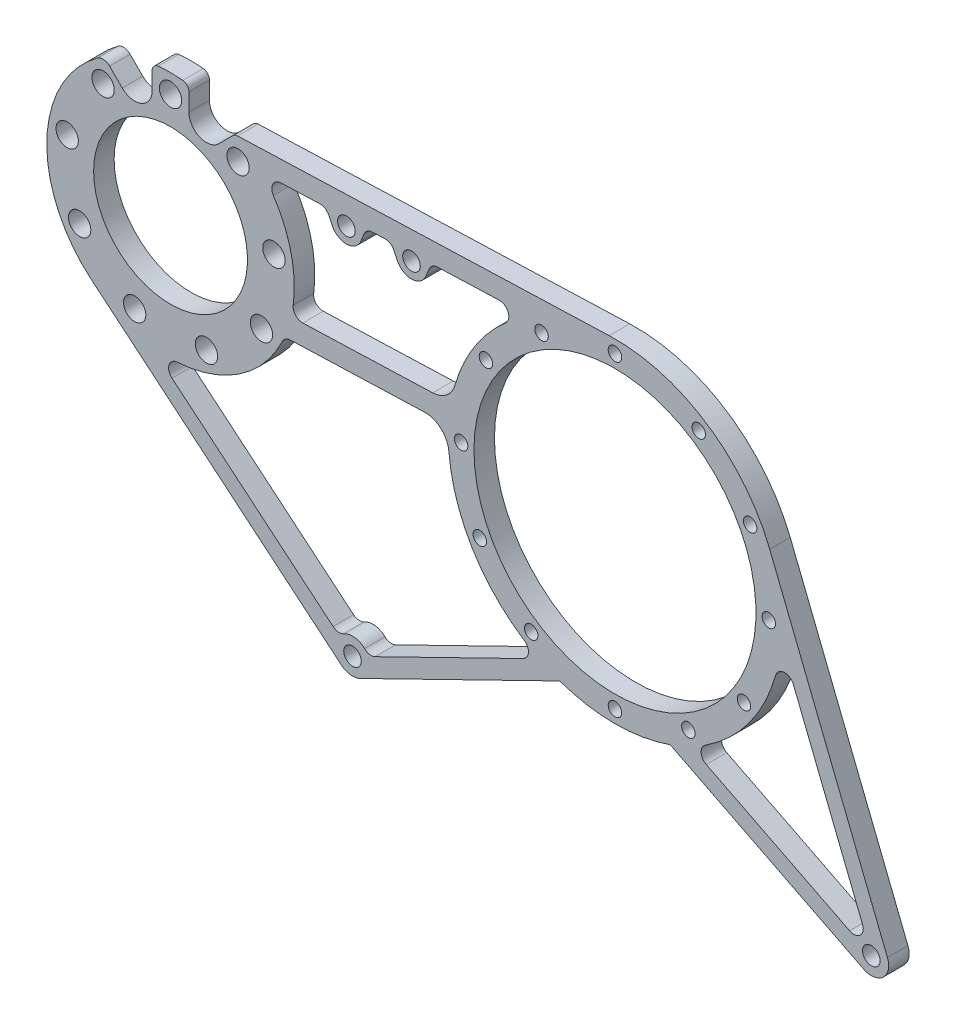
SolidWorks part; units mm, degrees
material "6061-T6 (SS)"
ref_plane "Front Plane" through (0, 0, 0) normal (0, 0, 1) x (1, 0, 0)
ref_plane "Top Plane" through (0, 0, 0) normal (0, 1, 0) x (1, 0, 0)
ref_plane "Right Plane" through (0, 0, 0) normal (1, 0, 0) x (0, 0, -1)
sketch "Sketch2" plane through (0, 0, 0) normal (0, 0, 1) x (1, 0, 0)
  line L0 (-114.3, 107.95) -> (-114.3, 95.25) construction
  line L1 (-308.8661, 91.7104) -> (-215.9264, 14.1075)
  line L3 (-13.0706, 21.4387) -> (-56.8054, 130.918)
  line L4 (-208.9705, 13.2659) -> (-134.815, 49.5352)
  line L5 (-21.9498, 13.301) -> (-93.785, 49.5352)
  line L7 (-254.4917, 165.0591) -> (-116.4363, 169.8256)
  line L10 (-286.2388, 170.2207) -> (-286.2388, 163.648)
  line L11 (-299.2388, 163.648) -> (-299.2388, 164.225)
  line L12 (-256.2001, 164.3167) -> (-261.465, 159.0518)
  line L13 (-272.5612, 163.648) -> (-272.5612, 170.2207)
  line L14 (-286.2388, 170.2207) -> (-286.2388, 163.648)
  line L16 (-256.2001, 164.3167) -> (-261.465, 159.0518)
  line L17 (-272.5612, 163.648) -> (-272.5612, 170.2207)
  line L84 (-302.5999, 164.3167) -> (-297.335, 159.0518) construction
  line L85 (-302.028, 163.7448) -> (-297.335, 159.0518)
  circle A0 centre (-279.4, 127) radius 28.575
  circle A1 centre (-114.3, 95.25) radius 36 construction
  circle A2 centre (0, 0) radius 12.7 construction
  circle A3 centre (-228.6, 0) radius 12.7 construction
  arc A5 (-134.815, 49.5352) -> (-93.785, 49.5352) centre (-114.3, 107.95) ccw
  circle A6 centre (-19.05, 19.05) radius 3.2639
  circle A7 centre (-211.7995, 19.05) radius 3.2639
  arc A8 (-215.9264, 14.1075) -> (-208.9705, 13.2659) centre (-211.7995, 19.05) ccw
  arc A9 (-21.9498, 13.301) -> (-13.0706, 21.4387) centre (-19.05, 19.05) ccw
  circle A10 centre (-114.3, 107.95) radius 52.3875
  arc A11 (-56.8054, 130.918) -> (-116.4363, 169.8256) centre (-114.3, 107.95) ccw
  arc A12 (-134.815, 49.5352) -> (-116.4363, 169.8256) centre (-114.3, 107.95) ccw construction
  arc A13 (-308.8661, 91.7104) -> (-306.5609, 164.0931) centre (-279.4, 127) cw
  arc A20 (-299.2388, 163.648) -> (-286.2388, 163.648) centre (-292.7388, 163.648) ccw
  arc A21 (-299.2388, 164.225) -> (-303.0875, 166.4019) centre (-301.7788, 164.225) ccw
  arc A22 (-303.0875, 166.4019) -> (-252.9423, 164.5979) centre (-279.4, 127) ccw
  arc A23 (-252.9423, 164.5979) -> (-256.2001, 164.3167) centre (-254.4041, 162.5207) ccw
  arc A24 (-272.5612, 163.648) -> (-261.465, 159.0518) centre (-266.0612, 163.648) ccw
  arc A25 (-272.5612, 170.2207) -> (-274.8498, 172.7483) centre (-275.1012, 170.2207) ccw
  arc A26 (-274.8498, 172.7483) -> (-283.9502, 172.7483) centre (-279.4, 127) ccw
  arc A27 (-283.9502, 172.7483) -> (-286.2388, 170.2207) centre (-283.6988, 170.2207) ccw
  arc A28 (-297.335, 159.0518) -> (-286.2388, 163.648) centre (-292.7388, 163.648) ccw
  arc A31 (-254.4917, 165.0591) -> (-256.2001, 164.3167) centre (-254.4041, 162.5207) ccw
  arc A32 (-272.5612, 163.648) -> (-261.465, 159.0518) centre (-266.0612, 163.648) ccw
  arc A33 (-272.5612, 170.2207) -> (-274.8498, 172.7483) centre (-275.1012, 170.2207) ccw
  arc A34 (-274.8498, 172.7483) -> (-283.9502, 172.7483) centre (-279.4, 127) ccw
  arc A35 (-283.9502, 172.7483) -> (-286.2388, 170.2207) centre (-283.6988, 170.2207) ccw
  arc A166 (-306.5609, 164.0931) -> (-302.028, 163.7448) centre (-304.4975, 161.2752) cw
  dimension "D1" = 25.4
  dimension "D2" = 25.4
  dimension "D8" = 57.15
  dimension "D9" = 72
  dimension "D10" = 3.4925
  dimension "D12" = 123.825
  dimension "D13" = 6.5278
  dimension "D16" = 6.5278
  dimension "D18" = 3.175
  dimension "D20" = 104.775
  dimension "D3" = 228.6
  dimension "D4" = 114.3
  dimension "D5" = 95.25
  dimension "D6" = 279.4
  dimension "D7" = 127
  dimension "D11" = 12.7
  dimension "D14" = 19.05
  dimension "D15" = 19.05
  dimension "D17" = 25.4
  dimension "D19" = 82.55
  dimension "D21" = 0
extrude "Boss-Extrude1" add sketch "Sketch2" along normal blind 7.62
sketch "Sketch3" plane through (0, 0, 7.62) normal (0, 0, 1) x (1, 0, 0)
  line L0 (-279.4, 127) -> (-279.4, 166) construction
  line L1 (-114.3, 107.95) -> (-114.3, 165.1) construction
  line L2 (-114.3, 107.95) -> (-83.1739, 155.88) construction
  line L3 (-114.3, 107.95) -> (-64.0756, 135.2196) construction
  circle A0 centre (-279.4, 127) radius 39 construction
  circle A1 centre (-279.4, 166) radius 4.15
  circle A2 centre (-254.3313, 156.8757) radius 4.15
  circle A3 centre (-240.9925, 133.7723) radius 4.15
  circle A4 centre (-245.625, 107.5) radius 4.15
  circle A5 centre (-266.0612, 90.352) radius 4.15
  circle A6 centre (-292.7388, 90.352) radius 4.15
  circle A7 centre (-313.175, 107.5) radius 4.15
  circle A8 centre (-317.8075, 133.7723) radius 4.15
  circle A9 centre (-304.4687, 156.8757) radius 4.15
  circle A10 centre (-114.3, 107.95) radius 57.15 construction
  circle A11 centre (-114.3, 165.1) radius 2.5
  circle A21 centre (-57.15, 107.95) radius 2.5
  circle A22 centre (-114.3, 50.8) radius 2.5
  circle A23 centre (-171.45, 107.95) radius 2.5
  circle A24 centre (-83.1739, 155.88) radius 2.5
  circle A25 centre (-64.0756, 135.2196) radius 2.5
  circle A26 centre (-66.37, 76.8239) radius 2.5
  circle A27 centre (-87.0304, 57.7256) radius 2.5
  circle A28 centre (-145.4261, 60.02) radius 2.5
  circle A29 centre (-164.5244, 80.6804) radius 2.5
  circle A30 centre (-162.23, 139.0761) radius 2.5
  circle A31 centre (-141.5696, 158.1744) radius 2.5
  point P24 (-279.4, 127)
  point P36 (-114.3, 107.95)
  point P48 (-114.3, 107.95)
  point P54 (-114.3, 107.95)
  dimension "D1" = 78
  dimension "D2" = 8.3
  dimension "D4" = 114.3
  dimension "D5" = 5
  dimension "D7" = 33
  dimension "D8" = 61.5
  dimension "D3" = 9
  dimension "D6" = 4
  dimension "D9" = 4
extrude "Cut-Extrude1" cut sketch "Sketch3" against normal through all both and the other way through all
sketch "Sketch4" plane through (0, 0, 7.62) normal (0, 0, 1) x (1, 0, 0)
  line L0 (-278.8626, 74.9306) -> (-219.0181, 24.9616)
  line L1 (-48.0193, 91.8071) -> (-22.3039, 27.4349)
  line L2 (-308.8661, 91.7104) -> (-215.9264, 14.1075) construction
  line L3 (-148.3931, 49.9629) -> (-203.3792, 23.0694)
  line L4 (-208.9705, 13.2659) -> (-134.815, 49.5352) construction
  line L5 (-238.4024, 157.9901) -> (-157.3456, 160.7887)
  line L7 (-80.3879, 49.8896) -> (-27.12, 23.021)
  line L8 (-93.785, 49.5352) -> (-21.9498, 13.301) construction
  line L9 (-13.0706, 21.4387) -> (-56.8054, 130.918) construction
  line L10 (-230.2469, 116.9721) -> (-182.0371, 118.6366)
  line L11 (-234.876, 109.1877) -> (-185.1604, 110.9042)
  line L13 (-116.4363, 169.8256) -> (-254.4917, 165.0591) construction
  arc A0 (-233.8293, 120.9241) -> (-237.9076, 107.2013) centre (-279.4, 127) ccw construction
  arc A1 (-175.9949, 102.7641) -> (-173.8002, 125.0639) centre (-114.3, 107.95) ccw construction
  circle A2 centre (-19.05, 19.05) radius 6.4389 construction
  circle A3 centre (-211.7995, 19.05) radius 6.4389 construction
  arc A4 (-306.5609, 164.0931) -> (-308.8661, 91.7104) centre (-279.4, 127) ccw construction
  arc A5 (-241.1849, 152.5581) -> (-233.8293, 120.9241) centre (-279.4, 127) cw
  arc A6 (-154.933, 154.6631) -> (-173.8002, 125.0639) centre (-114.3, 107.95) ccw
  arc A7 (-54.6287, 91.4427) -> (-80.7099, 55.9417) centre (-114.3, 107.95) cw
  arc A8 (-157.3456, 160.7887) -> (-154.933, 154.6631) centre (-157.2251, 157.2982) cw
  arc A9 (-238.4024, 157.9901) -> (-241.1849, 152.5581) centre (-238.2818, 154.4997) ccw
  arc A10 (-278.8626, 74.9306) -> (-276.8202, 81.0984) centre (-276.6242, 77.6114) cw
  arc A11 (-148.0251, 56.0292) -> (-148.3931, 49.9629) centre (-149.9276, 53.1003) cw
  arc A12 (-80.3879, 49.8896) -> (-80.7099, 55.9417) centre (-78.8151, 53.0079) cw
  arc A13 (-48.0193, 91.8071) -> (-54.6287, 91.4427) centre (-51.2626, 90.5115) ccw
  arc A14 (-27.12, 23.021) -> (-22.3039, 27.4349) centre (-25.5472, 26.1393) ccw
  arc A15 (-215.0283, 24.6208) -> (-207.3352, 23.69) centre (-211.7995, 19.05) cw
  arc A16 (-203.3792, 23.0694) -> (-207.3352, 23.69) centre (-204.9137, 26.2067) cw
  arc A17 (-219.0181, 24.9616) -> (-215.0283, 24.6208) centre (-216.7797, 27.6425) ccw
  arc A18 (-237.9076, 107.2013) -> (-276.8202, 81.0984) centre (-279.4, 127) cw
  arc A19 (-175.9949, 102.7641) -> (-148.0251, 56.0292) centre (-114.3, 107.95) ccw
  arc A22 (-230.2469, 116.9721) -> (-233.8293, 120.9241) centre (-230.3674, 120.4625) cw
  arc A23 (-234.876, 109.1877) -> (-237.9076, 107.2013) centre (-234.7555, 105.6973) ccw
  arc A24 (-182.0371, 118.6366) -> (-173.8002, 125.0639) centre (-182.3438, 127.5213) ccw
  arc A25 (-185.1604, 110.9042) -> (-175.9949, 102.7641) centre (-184.8537, 102.0195) cw
  point P40 (-245.2273, 157.7545)
  point P43 (-286.9003, 81.6419)
  point P46 (-142.5125, 52.8391)
  point P50 (-52.5701, 103.1988)
  point P56 (-216.7985, 23.1083)
  dimension "D1" = 61.9125
  dimension "D2" = 12.8778
  dimension "D3" = 12.8778
  dimension "D9" = 3.4925
  dimension "D10" = 61.9125
  dimension "D11" = 3.4925
  dimension "D14" = 8.89
  dimension "D15" = 8.89
  dimension "D4" = 6.35
  dimension "D5" = 6.35
  dimension "D6" = 7.62
  dimension "D7" = 6.35
  dimension "D8" = 6.35
  dimension "D12" = 41.275
  dimension "D13" = 7.62
extrude "Cut-Extrude2" cut sketch "Sketch4" against normal through all both and the other way through all
sketch "Sketch6" plane through (0, 0, 7.62) normal (0, 0, 1) x (1, 0, 0)
  line L0 (-256.2001, 164.3171) -> (-261.465, 159.0522)
  line L1 (-272.5612, 163.6484) -> (-272.5612, 170.2212)
  line L2 (-286.2388, 170.2212) -> (-286.2388, 163.6484)
  line L3 (-299.2388, 163.6484) -> (-299.2392, 164.2676)
  arc A0 (-303.0807, 166.406) -> (-252.9493, 164.6028) centre (-279.4, 127) ccw
  arc A1 (-252.9493, 164.6028) -> (-256.2001, 164.3171) centre (-254.4043, 162.5208) ccw
  arc A2 (-272.5612, 163.6484) -> (-261.465, 159.0522) centre (-266.0612, 163.6484) ccw
  arc A3 (-272.5612, 170.2212) -> (-274.8498, 172.7487) centre (-275.1012, 170.2212) ccw
  arc A4 (-274.8498, 172.7487) -> (-283.9502, 172.7487) centre (-279.4, 127.0004) ccw
  arc A5 (-283.9502, 172.7487) -> (-286.2388, 170.2212) centre (-283.6988, 170.2212) ccw
  arc A6 (-299.2388, 163.6484) -> (-286.2388, 163.6484) centre (-292.7388, 163.6484) ccw
  arc A7 (-299.2392, 164.2676) -> (-303.0807, 166.406) centre (-301.7788, 164.225) ccw
  dimension "D1" = 45.974
  dimension "D2" = 2.54
  dimension "D4" = 6.5
  dimension "D5" = 6.5
  dimension "D6" = 2.54
  dimension "D7" = 2.54
  dimension "D8" = 45.974
  dimension "D9" = 2.54
  dimension "D3" = 7.4457
  dimension "D10" = 6.5727
ref_plane "Plane3" through (0, 0, 3.81) normal (0, 0, 1) x (1, 0, 0)
ref_axis "Axis1" through (-279.4, 127, 7.62) along (0, 0, -1)
ref_plane "Plane1" through (-279.4, 0, 0) normal (1, 0, 0) x (0, 0, -1)
ref_axis "Axis2" through (-114.3, 107.95, 7.62) along (0, 0, -1)
ref_plane "Plane2" through (-114.3, 0, 0) normal (1, 0, 0) x (0, 0, -1)
split line "Split Line1" [suppressed]
split line "Split Line2" [suppressed]
sketch "Sketch7" [suppressed] plane through (0, 0, 3.81) normal (0, 0, 1) x (1, 0, 0)
  arc A0 (-279.4, 155.575) -> (-279.4, 98.425) centre (-279.4, 127) ccw construction
  arc A1 (-279.4, 98.425) -> (-279.4, 155.575) centre (-279.4, 127) ccw construction
  arc A2 (-279.4, 155.575) -> (-279.4, 98.425) centre (-279.4, 127) ccw
  arc A3 (-279.4, 98.425) -> (-279.4, 155.575) centre (-279.4, 127) ccw
  arc A4 (-114.3, 55.5625) -> (-114.3, 160.3375) centre (-114.3, 107.95) ccw construction
  arc A5 (-114.3, 160.3375) -> (-114.3, 55.5625) centre (-114.3, 107.95) ccw construction
  arc A6 (-114.3, 55.5625) -> (-114.3, 160.3375) centre (-114.3, 107.95) ccw
  arc A7 (-114.3, 160.3375) -> (-114.3, 55.5625) centre (-114.3, 107.95) ccw
  point P4 (-279.4, 127)
  point P8 (-114.3, 107.95)
sketch "Sketch11" plane through (0, 0, 0) normal (0, 0, -1) x (-1, 0, 0)
  line L0 (157.3456, 160.7887) -> (238.4024, 157.9901) construction
  line L1 (182.3987, 159.9237) -> (187.9461, 159.7321)
  line L2 (184.5049, 154.9364) -> (183.3433, 157.8152)
  line L3 (189.8872, 157.1081) -> (189.9754, 159.6621) construction
  line L4 (195.1068, 154.5703) -> (196.4642, 157.3621)
  line L5 (201.9791, 156.6907) -> (202.2057, 163.2538) construction
  line L6 (189.8872, 157.1081) -> (214.071, 156.2732) construction
  line L7 (208.6887, 154.1014) -> (207.5271, 156.9802)
  line L8 (214.071, 156.2732) -> (214.1591, 158.8271)
  line L9 (219.2906, 153.7354) -> (220.648, 156.5272)
  line L10 (221.7357, 158.5656) -> (206.5825, 159.0887)
  line L11 (223.9095, 158.4905) -> (221.7357, 158.5656)
  line L12 (197.552, 159.4005) -> (199.7256, 159.3254)
  line L13 (206.5825, 159.0887) -> (204.4088, 159.1638)
  line L14 (182.3987, 159.9237) -> (180.2251, 159.9987)
  line L15 (192.0046, 159.592) -> (197.552, 159.4005)
  arc A0 (187.9461, 159.7321) -> (192.0046, 159.592) centre (189.8872, 157.1081) ccw
  circle A1 centre (214.071, 156.2732) radius 3.3 construction
  arc A2 (184.5049, 154.9364) -> (195.1068, 154.5703) centre (189.8872, 157.1081) ccw
  circle A4 centre (189.8872, 157.1081) radius 5.8039 construction
  circle A5 centre (189.8872, 157.1081) radius 3.2639 construction
  arc A6 (219.2906, 153.7354) -> (208.6887, 154.1014) centre (214.071, 156.2732) cw
  arc A7 (216.1884, 158.7571) -> (212.1299, 158.8972) centre (214.071, 156.2732) cw
  arc A8 (183.3433, 157.8152) -> (180.2251, 159.9987) centre (180.1045, 156.5083) ccw
  arc A9 (223.9095, 158.4905) -> (220.648, 156.5272) centre (223.7889, 155.0001) ccw
  arc A10 (207.5271, 156.9802) -> (204.4088, 159.1638) centre (204.2883, 155.6733) ccw
  arc A11 (199.7256, 159.3254) -> (196.4642, 157.3621) centre (199.6051, 155.835) ccw
  dimension "D1" = 6.5278
  dimension "D3" = 3.4925
  dimension "D2" = 2.54
extrude "Boss-Extrude2" add sketch "Sketch11" against normal up to surface (7.62 mm away) contours A10 L7 A6 L9 A9 L11 L10 A7 L13 | A11 L12 L15 A0 L1 L14 A8 L2 A2 L4 region at (-185.1651, 159.6145, 0) region at (-208.3059, 155.6207, 0) up to face at (-201.2925, 138.6418, 7.62)
sketch "Sketch12" plane through (0, 0, 0) normal (0, 0, -1) x (-1, 0, 0)
  circle A1 centre (189.8872, 157.1081) radius 3.2639
  circle A2 centre (214.071, 156.2732) radius 3.2639
extrude "Cut-Extrude3" cut sketch "Sketch12" against normal through all both and the other way through all
sketch "Sketch13" plane through (0, 0, 3.81) normal (0, 0, 1) x (1, 0, 0)
  point P0 (-168.529, 91.0245)
ref_point "Point2"
ref_axis "Axis3" through (-168.529, 91.0245, 3.81) along (0, 0, 1)
